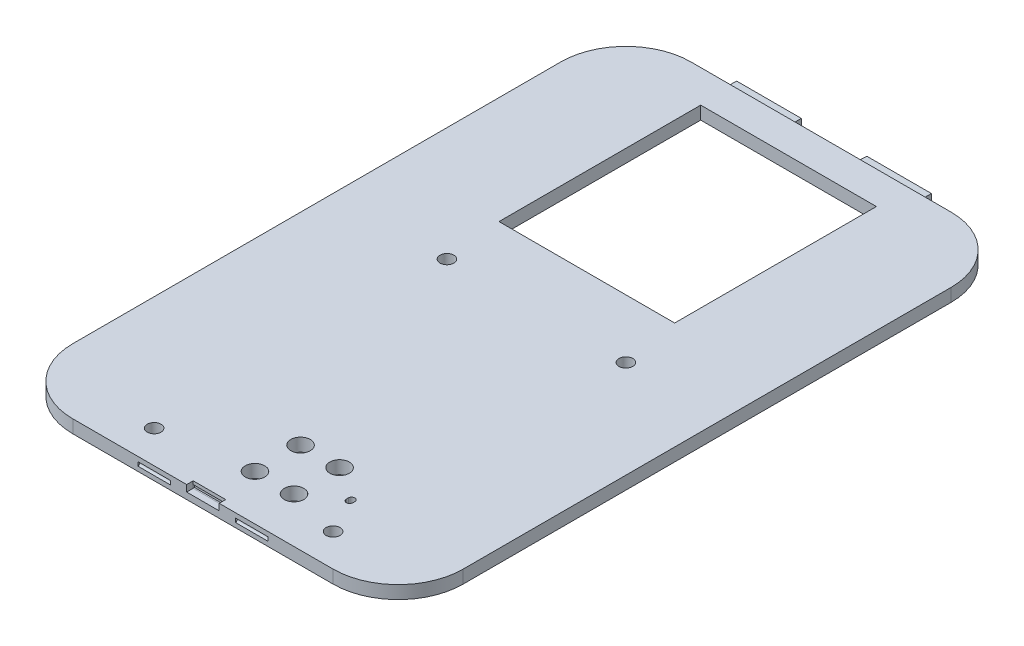
SolidWorks part; units mm, degrees
ref_plane "Front Plane" through (0, 0, 0) normal (0, 0, 1) x (1, 0, 0)
ref_plane "Top Plane" through (0, 0, 0) normal (0, 1, 0) x (1, 0, 0)
ref_plane "Right Plane" through (0, 0, 0) normal (1, 0, 0) x (0, 0, -1)
sketch "Sketch2" plane through (0, 0, 0) normal (0, 1, 0) x (1, 0, 0)
  line L0 (-25.4, -60.325) -> (25.4, -60.325)
  line L1 (-38.1, -47.625) -> (-38.1, 47.625)
  line L2 (38.1, -47.625) -> (38.1, 47.625)
  line L3 (-25.4, 60.325) -> (25.4, 60.325)
  line L4 (-38.1, -60.325) -> (38.1, 60.325) construction
  line L5 (38.1, -60.325) -> (-38.1, 60.325) construction
  arc A0 (-38.1, 47.625) -> (-25.4, 60.325) centre (-25.4, 47.625) cw
  arc A1 (38.1, 47.625) -> (25.4, 60.325) centre (25.4, 47.625) ccw
  arc A2 (25.4, -60.325) -> (38.1, -47.625) centre (25.4, -47.625) ccw
  arc A3 (-38.1, -47.625) -> (-25.4, -60.325) centre (-25.4, -47.625) ccw
  dimension "D3" = 12.7
  dimension "D4" = 12.7
  dimension "D1" = 120.65
  dimension "D2" = 76.2
extrude "top" add sketch "Sketch2" along normal blind 2.54
sketch "PCBOutline" plane through (0, 2.54, 2.54) normal (0, 1, 0) x (1, 0, 0)
  line L0 (-25.4, -57.785) -> (25.4, -57.785) construction
  line L1 (-19.05, -55.245) -> (22.86, -55.245)
  line L2 (-19.05, -55.245) -> (-19.05, 9.525)
  line L3 (-19.05, 9.525) -> (22.86, 9.525)
  line L4 (22.86, -55.245) -> (22.86, 9.525)
  line L5 (-38.1, 50.165) -> (-38.1, -45.085) construction
  dimension "D1" = 41.91
  dimension "D2" = 64.77
  dimension "D3" = 2.54
  dimension "D4" = 19.05
sketch "Sketch7" plane through (0, 2.54, 0) normal (0, 1, 0) x (1, 0, 0)
  line L1 (1.27, -51.435) -> (8.89, -51.435) construction
  line L2 (1.27, -51.435) -> (1.27, -42.545) construction
  line L3 (-19.05, -57.785) -> (-19.05, 6.985) construction
  line L4 (15.494, -46.7995) -> (15.494, -47.1805) construction
  line L5 (16.129, -46.7995) -> (16.129, -47.1805)
  line L6 (14.859, -46.7995) -> (14.859, -47.1805)
  line L7 (1.27, -46.99) -> (15.494, -46.99) construction
  line L8 (-19.05, -57.785) -> (22.86, -57.785) construction
  circle A0 centre (1.27, -51.435) radius 1.905
  circle A1 centre (8.89, -51.435) radius 1.905
  circle A2 centre (8.89, -42.545) radius 1.905
  circle A3 centre (1.27, -42.545) radius 1.905
  arc A4 (16.129, -46.7995) -> (14.859, -46.7995) centre (15.494, -46.7995) ccw
  arc A5 (14.859, -47.1805) -> (16.129, -47.1805) centre (15.494, -47.1805) ccw
  point P6 (15.494, -46.99)
  dimension "D7" = 3.81
  dimension "D4" = 7.62
  dimension "D5" = 8.89
  dimension "D6" = 20.32
  dimension "D8" = 14.224
  dimension "D9" = 0.381
  dimension "D10" = 1.27
  dimension "D11" = 6.35
  dimension "D2" = 2
  dimension "D3" = 2
extrude "ButtonLEDCut" cut sketch "Sketch7" against normal through all
sketch "Sketch8" plane through (0, 2.54, 0) normal (0, 1, 0) x (1, 0, 0)
  line L0 (0, 0) -> (0, 60.325) construction
  line L1 (25.4, 60.325) -> (-25.4, 60.325) construction
  line L2 (-17.145, 14.605) -> (-17.145, 53.975)
  line L3 (-17.145, 14.605) -> (17.145, 14.605)
  line L4 (-17.145, 53.975) -> (17.145, 53.975)
  line L5 (17.145, 14.605) -> (17.145, 53.975)
  line L6 (-17.145, 14.605) -> (17.145, 53.975) construction
  line L7 (-17.145, 53.975) -> (17.145, 14.605) construction
  line L8 (-17.145, 19.685) -> (17.145, 19.685) construction
  point P6 (0, 34.29)
  dimension "D1" = 6.35
  dimension "D2" = 34.29
  dimension "D3" = 34.29
  dimension "D4" = 39.37
extrude "SolarCut" cut sketch "Sketch8" against normal through all
sketch "Mounting Holes" plane through (0, 2.54, 2.54) normal (0, 1, 0) x (1, 0, 0)
  line L2 (-19.05, -55.245) -> (-19.05, 9.525) construction
  line L3 (-19.05, -55.245) -> (22.86, -55.245) construction
  point P0 (-15.875, 5.715)
  point P2 (19.05, 5.715)
  point P4 (19.05, -51.435)
  point P6 (-15.875, -51.435)
  dimension "D1" = 3.175
  dimension "D2" = 3.81
  dimension "D3" = 34.925
  dimension "D4" = 57.15
hole_wizard "#6-32 Tapped Hole1" positions "Sketch12" profile "Sketch11" tap size "#6-32" standard "ANSI Inch"
sketch "Sketch12" plane through (0, 2.54, 0) normal (0, 1, 0) x (1, 0, 0)
  point P0 (-15.875, 3.175)
  point P3 (19.05, 3.175)
  point P6 (19.05, -53.975)
  point P9 (-15.875, -53.975)
sketch "Sketch11" plane through (-15.875, 2.54, -3.175) normal (1, 0, 0) x (0, 0, 1)
  line L0 (0, 0) -> (0, 11.9887)
  line L1 (0, 11.9887) -> (1.3525, 11.176)
  line L2 (1.3525, 11.176) -> (1.3525, 0)
  line L5 (1.3525, 0) -> (0, 0)
  line L10 (0, 11.9887) -> (-1.3526, 11.176) construction
  line L11 (0, -6.35) -> (0, 107.95) construction
  dimension "Tap Drill Dia." = 2.7051
  dimension "Tap Drill Depth" = 11.176
  dimension "Drill Angle" = 118
sketch "Sketch13" plane through (0, 0, -60.325) normal (0, 0, -1) x (-1, 0, 0)
  line L0 (-25.4, 0) -> (25.4, 0) construction
  line L1 (-19.05, 0) -> (-6.35, 0)
  line L2 (-19.05, 0) -> (-19.05, 1.27)
  line L3 (-19.05, 1.27) -> (-6.35, 1.27)
  line L4 (-6.35, 0) -> (-6.35, 1.27)
  line L5 (0, 0) -> (0, 2.54) construction
  line L6 (-25.4, 2.54) -> (25.4, 2.54) construction
  line L7 (19.05, 0) -> (6.35, 0)
  line L8 (6.35, 0) -> (6.35, 1.27)
  line L9 (19.05, 1.27) -> (6.35, 1.27)
  line L10 (19.05, 0) -> (19.05, 1.27)
  dimension "D1" = 6.35
  dimension "D2" = 1.27
  dimension "D3" = 12.7
extrude "Body Tabs" add sketch "Sketch13" along normal blind 2.54 draft 1
sketch "Sketch14" plane through (0, 2.54, 0) normal (0, 1, 0) x (1, 0, 0)
  line L0 (0, -60.325) -> (0, -56.9665) construction
  line L1 (-25.4, -60.325) -> (25.4, -60.325) construction
  line L3 (-3.175, -60.325) -> (3.175, -60.325)
  line L4 (-3.175, -60.325) -> (-3.175, -59.055)
  line L5 (-3.175, -59.055) -> (3.175, -59.055)
  line L6 (3.175, -60.325) -> (3.175, -59.055)
  dimension "D1" = 6.35
  dimension "D2" = 1.27
extrude "Flat Head Hole" cut sketch "Sketch14" against normal blind 1.27
sketch "Sketch15" plane through (0, 0, 60.325) normal (0, 0, 1) x (1, 0, 0)
  line L0 (0, 0) -> (0, 2.54) construction
  line L1 (-12.7, 1.651) -> (-6.35, 1.651)
  line L2 (-12.7, 1.651) -> (-12.7, 0.889)
  line L3 (-12.7, 0.889) -> (-6.35, 0.889)
  line L4 (-6.35, 1.651) -> (-6.35, 0.889)
  line L5 (3.175, 2.54) -> (-3.175, 2.54) construction
  line L6 (0, 1.27) -> (-25.4, 1.27) construction
  line L7 (-25.4, 2.54) -> (-25.4, 0) construction
  line L8 (-25.4, 1.27) -> (25.4, 1.27) construction
  line L9 (25.4, 2.54) -> (25.4, 0) construction
  line L10 (12.7, 1.651) -> (12.7, 0.889)
  line L11 (12.7, 0.889) -> (6.35, 0.889)
  line L12 (6.35, 1.651) -> (6.35, 0.889)
  line L13 (12.7, 1.651) -> (6.35, 1.651)
  point P16 (-6.35, 1.27)
  dimension "D1" = 0.762
  dimension "D2" = 6.35
  dimension "D3" = 6.35
extrude "Hold Grpoves" cut sketch "Sketch15" against normal blind 0.381
fillet "Hold Fillets" radius 0.381 4 edges at (9.525, 1.651, 59.944) (9.525, 0.889, 59.944) (-9.525, 0.889, 59.944) (-9.525, 1.651, 59.944)
sketch "Sketch16" plane through (0, 0, 59.055) normal (0, 0, 1) x (1, 0, 0)
  line L0 (3.175, 1.27) -> (3.175, 2.54) construction
  line L1 (-3.175, 1.27) -> (3.175, 1.27)
  line L2 (-3.175, 1.27) -> (-3.175, 1.905)
  line L3 (-3.175, 1.905) -> (3.175, 1.905)
  line L4 (3.175, 1.27) -> (3.175, 1.905)
extrude "Flat Head Support" cut sketch "Sketch16" against normal blind 0.254 draft 2
